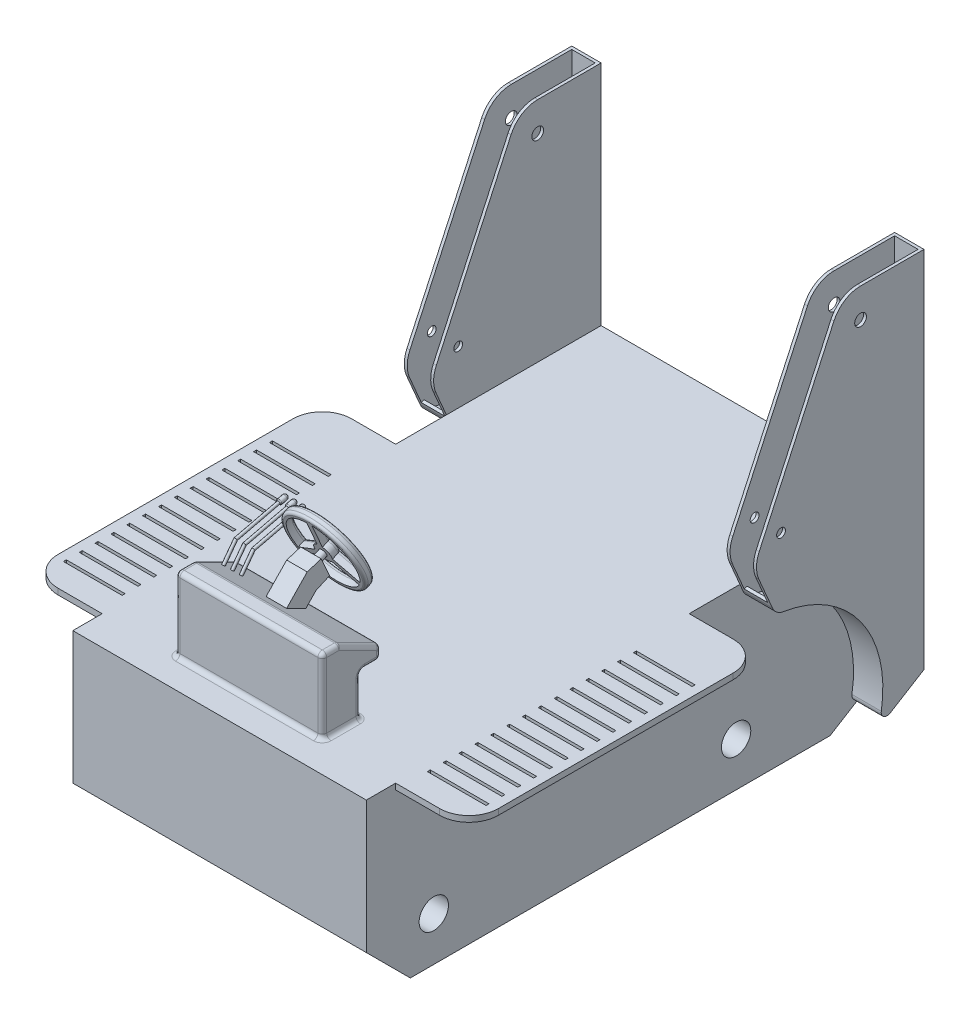
SolidWorks part; units mm, degrees
ref_plane "Front Plane" through (0, 0, 0) normal (0, 0, 1) x (1, 0, 0)
ref_plane "Top Plane" through (0, 0, 0) normal (0, 1, 0) x (1, 0, 0)
ref_plane "Right Plane" through (0, 0, 0) normal (1, 0, 0) x (0, 0, -1)
sketch "Sketch2" plane through (0, 0, 0) normal (1, 0, 0) x (0, 0, -1)
  line L0 (-865, 600) -> (935, 600)
  line L1 (935, 600) -> (935, 135)
  line L2 (935, 135) -> (715, 0)
  line L3 (715, 0) -> (-715, 0)
  line L4 (-715, 0) -> (-865, 150)
  line L5 (-865, 150) -> (-865, 600)
  circle A0 centre (-635, 150) radius 50
  circle A1 centre (395, 150) radius 50
  dimension "D8" = 100
  dimension "D1" = 1800
  dimension "D2" = 600
  dimension "D3" = 150
  dimension "D4" = 150
  dimension "D5" = 220
  dimension "D6" = 135
  dimension "D7" = 1030
  dimension "D9" = 150
  dimension "D10" = 540
extrude "Boss-Extrude1" add sketch "Sketch2" along normal mid plane 1000
sketch "Sketch3" plane through (500, 0, 0) normal (1, 0, 0) x (0, 0, -1)
  line L0 (935, 135) -> (935, 1375)
  line L1 (935, 1375) -> (719.0464, 1375)
  line L2 (628.213, 1316.8244) -> (373.5875, 763.8338)
  line L3 (372.5065, 682.6174) -> (418.6781, 574.8835)
  line L4 (935, 135) -> (819.8142, 64.3178)
  line L5 (715, 0) -> (935, 135) construction
  arc A0 (819.8142, 64.3178) -> (789.6227, 84.6326) centre (809.3539, 81.3643) cw
  arc A1 (789.6227, 84.6326) -> (456.8981, 545.1818) centre (395, 150) ccw
  circle A2 centre (395, 150) radius 50 construction
  arc A3 (719.0464, 1375) -> (628.213, 1316.8244) centre (719.0464, 1275) ccw
  arc A4 (373.5875, 763.8338) -> (372.5065, 682.6174) centre (464.421, 722.0093) ccw
  arc A5 (418.6781, 574.8835) -> (456.8981, 545.1818) centre (464.6354, 594.5795) ccw
  point P16 (655, 1375)
  point P19 (355, 723.4658)
  point P22 (430, 548.4658)
  dimension "D5" = 400
  dimension "D6" = 20
  dimension "D8" = 100
  dimension "D9" = 100
  dimension "D10" = 50
  dimension "D1" = 1240
  dimension "D2" = 280
  dimension "D3" = 175
  dimension "D4" = 75
  dimension "D7" = 35
extrude "Boss-Extrude2" add sketch "Sketch3" along normal blind 10 separate body
sketch "Sketch5" plane through (510, 0, 0) normal (1, 0, 0) x (0, 0, -1)
  line L0 (935, 135) -> (935, 1375) construction
  line L1 (935, 600) -> (-865, 600) construction
  line L2 (935, 135) -> (935, 1375)
  line L3 (819.8142, 64.3178) -> (935, 135) construction
  line L4 (819.8142, 64.3178) -> (935, 135)
  line L5 (418.6781, 574.8835) -> (412.6282, 589)
  line L6 (372.5065, 682.6174) -> (418.6781, 574.8835) construction
  line L7 (427.8696, 578.8227) -> (421.8197, 592.9392)
  line L8 (814.584, 72.841) -> (925, 140.5963)
  line L9 (925, 140.5963) -> (925, 1375)
  line L10 (418.6781, 574.8835) -> (411.5081, 591.6137) construction
  line L11 (427.8696, 578.8227) -> (420.6995, 595.5529) construction
  line L12 (412.6282, 589) -> (421.8197, 592.9392)
  line L13 (925, 1375) -> (935, 1375)
  arc A1 (789.6227, 84.6326) -> (819.8142, 64.3178) centre (809.3539, 81.3643) ccw construction
  arc A2 (789.6227, 84.6326) -> (819.8142, 64.3178) centre (809.3539, 81.3643) ccw
  arc A3 (789.6227, 84.6326) -> (456.8981, 545.1818) centre (395, 150) ccw construction
  arc A4 (789.6227, 84.6326) -> (456.8981, 545.1818) centre (395, 150) ccw
  arc A5 (418.6781, 574.8835) -> (456.8981, 545.1818) centre (464.6354, 594.5795) ccw construction
  arc A6 (418.6781, 574.8835) -> (456.8981, 545.1818) centre (464.6354, 594.5795) ccw
  arc A7 (427.8696, 578.8227) -> (458.4456, 555.0613) centre (464.6354, 594.5795) ccw
  arc A8 (799.4883, 82.9984) -> (458.4456, 555.0613) centre (395, 150) ccw
  arc A9 (799.4883, 82.9984) -> (814.584, 72.841) centre (809.3539, 81.3643) ccw
  dimension "D2" = 11
  dimension "D1" = 10
extrude "Boss-Extrude3" add sketch "Sketch5" along normal blind 80
extrude "Boss-Extrude4" add sketch "Sketch3<2>" along normal blind 10 from offset 90
sketch "Sketch3<2>" plane through (500, 0, 0) normal (1, 0, 0) x (0, 0, -1) same geometry as "Sketch3"
mirror "Mirror7" about plane through (0, 0, 0) normal (1, 0, 0) of bodies 104
sketch "Sketch6" plane through (600, 0, 0) normal (1, 0, 0) x (0, 0, -1)
  line L0 (628.213, 1316.8244) -> (373.5875, 763.8338) construction
  circle A0 centre (719.0464, 1275) radius 20
  circle A1 centre (448.0114, 782.0093) radius 15
  arc A2 (373.5875, 763.8338) -> (372.5065, 682.6174) centre (464.421, 722.0093) ccw construction
  dimension "D1" = 30
  dimension "D3" = 60
  dimension "D4" = 40
  dimension "D2" = 60
extrude "Cut-Extrude1" cut sketch "Sketch6" against normal through all
sketch "Sketch7" plane through (0, 600, 0) normal (0, 1, 0) x (1, 0, 0)
  line L0 (0, 0) -> (0, -865) construction
  line L1 (500, -865) -> (-500, -865) construction
  line L2 (500, 935) -> (500, -865) construction
  line L3 (500, 235) -> (650, 235)
  line L4 (500, 235) -> (500, -765)
  line L5 (500, -765) -> (650, -765)
  line L6 (750, 135) -> (750, -665)
  line L7 (-750, 135) -> (-750, -665)
  line L8 (-500, -765) -> (-650, -765)
  line L9 (-500, 235) -> (-500, -765)
  line L10 (-500, 235) -> (-650, 235)
  arc A0 (650, -765) -> (750, -665) centre (650, -665) ccw
  arc A1 (650, 235) -> (750, 135) centre (650, 135) cw
  arc A2 (-650, 235) -> (-750, 135) centre (-650, 135) ccw
  arc A3 (-650, -765) -> (-750, -665) centre (-650, -665) cw
  point P13 (750, -765)
  point P16 (750, 235)
  point P25 (-750, 235)
  point P26 (-750, -765)
  dimension "D4" = 100
  dimension "D1" = 250
  dimension "D2" = 100
  dimension "D3" = 1000
extrude "Boss-Extrude6" add sketch "Sketch7" against normal blind 20
sketch "Sketch8" plane through (0, 600, 0) normal (0, 1, 0) x (1, 0, 0)
  line L0 (750, -665) -> (750, 135) construction
  line L1 (520, 35) -> (720, 35)
  line L2 (520, 35) -> (520, 25)
  line L3 (520, 25) -> (720, 25)
  line L4 (720, 35) -> (720, 25)
  line L5 (650, 235) -> (500, 235) construction
  line L6 (0, 0) -> (0, -250.1496) construction
  line L7 (-720, 35) -> (-720, 25)
  line L8 (-520, 25) -> (-720, 25)
  line L9 (-520, 35) -> (-520, 25)
  line L10 (-520, 35) -> (-720, 35)
  dimension "D1" = 200
  dimension "D2" = 30
  dimension "D3" = 10
  dimension "D4" = 200
extrude "Cut-Extrude2" cut sketch "Sketch8" against normal through all
pattern_linear "LPattern1" count 14 spacing 54 along (0, 0, 1) of "Cut-Extrude2"
sketch "Sketch9" plane through (0, 600, 0) normal (0, 1, 0) x (1, 0, 0)
  line L0 (500, -865) -> (-500, -865) construction
  line L1 (-250, -565) -> (250, -565)
  line L2 (-250, -565) -> (-250, -765)
  line L3 (-250, -765) -> (250, -765)
  line L4 (250, -565) -> (250, -765)
  line L5 (0, -565) -> (0, -765) construction
  point P9 (0, -665)
  point P10 (0, -565)
  dimension "D1" = 500
  dimension "D2" = 200
  dimension "D3" = 100
extrude "Boss-Extrude7" add sketch "Sketch9" along normal blind 253
sketch "Sketch10" plane through (250, 0, 0) normal (1, 0, 0) x (0, 0, -1)
  line L0 (-705, 853) -> (-565, 853)
  line L1 (-765, 853) -> (-565, 853) construction
  line L2 (-565, 853) -> (-565, 783)
  line L3 (-565, 853) -> (-565, 600) construction
  line L4 (-565, 783) -> (-705, 853)
  line L5 (-565, 740) -> (-635, 740)
  line L6 (-635, 740) -> (-635, 600)
  line L7 (-765, 600) -> (-565, 600) construction
  line L8 (-635, 600) -> (-565, 600)
  line L9 (-565, 600) -> (-565, 740)
  dimension "D1" = 70
  dimension "D2" = 140
  dimension "D3" = 140
  dimension "D4" = 70
extrude "Cut-Extrude3" cut sketch "Sketch10" against normal through all
fillet "Fillet1" radius 15 21 edges at (0, 600, 635) (0, 740, 635) (0, 853, 705) (-250, 600, 700) (-250, 670, 635) (-250, 740, 600) (-250, 818, 635) (-250, 853, 735) (0, 740, 565) (0, 783, 565) (-250, 761.5, 565) (-250, 726.5, 765) (0, 853, 765) (0, 600, 765) (250, 740, 600) (250, 670, 635) (250, 600, 700) (250, 726.5, 765) (250, 853, 735) (250, 818, 635) (250, 761.5, 565)
ref_plane "Plane1" through (-220, 0, 0) normal (-1, 0, 0) x (0, 0, 1)
sketch "Sketch12" plane through (-220, 0, 0) normal (-1, 0, 0) x (0, 0, 1)
  line L0 (573.2918, 787.1459) -> (701.8328, 851.4164) construction
  line L1 (631.5477, 816.2738) -> (589.8462, 872.4965)
  line L2 (589.8462, 872.4965) -> (443.9511, 907.3477)
  dimension "D1" = 140
  dimension "D2" = 100
  dimension "D3" = 150
  dimension "D4" = 70
  dimension "D5" = 80
ref_plane "Plane2" through (-220, 907.3477, 443.9511) normal (0, 0.2323, -0.9726) x (-1, 0, 0)
sketch "Sketch13" plane through (-220, 907.3477, 443.9511) normal (0, 0.2323, -0.9726) x (-1, 0, 0)
  circle A0 centre (0, 0) radius 5
  dimension "D1" = 10
sweep "Sweep1" add profiles "Sketch13" path "Sketch12"
sketch "Sketch14" plane through (-220, 907.3477, 443.9511) normal (0, 0.2323, -0.9726) x (-1, 0, 0)
  circle A0 centre (0, 0) radius 8.5
  dimension "D1" = 17
extrude "Boss-Extrude8" add sketch "Sketch14" along normal blind 30
fillet "Fillet2" radius 8.5 1 edges at (-220, 922.5853, 416.7469)
fillet "Fillet3" radius 3.5 1 edges at (-220, 915.6151, 445.926)
pattern_linear "LPattern2" count 3 spacing 30 along (1, 0, 0) of bodies 115
sketch "Sketch16" plane through (0, 0, 0) normal (1, 0, 0) x (0, 0, -1)
  line L0 (-671.4223, 836.2111) -> (-601.352, 908.9514)
  line L1 (-701.8328, 851.4164) -> (-573.2918, 787.1459) construction
  line L2 (-601.352, 908.9514) -> (-553.5549, 923.6293)
  line L3 (-553.5549, 923.6293) -> (-525.3675, 859.5553)
  line L4 (-525.3675, 859.5553) -> (-571.1346, 839.4215)
  line L5 (-571.1346, 839.4215) -> (-605.8229, 803.4115)
  line L6 (-605.8229, 803.4115) -> (-671.4223, 836.2111)
  line L7 (-708.541, 838) -> (-701.8328, 851.4164) construction
  dimension "D1" = 101
  dimension "D2" = 151
  dimension "D3" = 50
  dimension "D4" = 70
  dimension "D5" = 34
  dimension "D6" = 70
extrude "Boss-Extrude9" add sketch "Sketch16" along normal mid plane 70
sketch "Sketch17" plane through (0, -54.2681, 123.3593) normal (0, 0.4027, -0.9153) x (-1, 0, 0)
  line L0 (-35, 1068.3406) -> (35, 1068.3406) construction
  line L1 (35, 998.3406) -> (35, 1068.3406) construction
  circle A0 centre (0, 1033.3406) radius 12.5
  dimension "D1" = 25
  dimension "D2" = 35
  dimension "D3" = 35
extrude "Boss-Extrude10" add sketch "Sketch17" along normal blind 30
sketch "Sketch18" plane through (0, -42.1878, 95.899) normal (0, 0.4027, -0.9153) x (-1, 0, 0)
  line L2 (-9, 1149.9939) -> (-9, 1061.9587)
  line L3 (9, 1149.9939) -> (9, 1061.9587)
  line L4 (105.5247, 982.8081) -> (29.2841, 1026.8257)
  line L5 (96.5247, 967.2197) -> (20.2841, 1011.2372)
  line L6 (-96.5247, 967.2197) -> (-20.2841, 1011.2372)
  line L7 (-105.5247, 982.8081) -> (-29.2841, 1026.8257)
  circle A0 centre (0, 1033.3406) radius 135
  arc A1 (-9, 1149.9939) -> (-105.5247, 982.8081) centre (0, 1033.3406) ccw
  arc A2 (29.2841, 1026.8257) -> (9, 1061.9587) centre (0, 1033.3406) ccw
  arc A4 (-96.5247, 967.2197) -> (96.5247, 967.2197) centre (0, 1033.3406) ccw
  arc A5 (105.5247, 982.8081) -> (9, 1149.9939) centre (0, 1033.3406) ccw
  arc A6 (-9, 1061.9587) -> (-29.2841, 1026.8257) centre (0, 1033.3406) ccw
  arc A7 (-20.2841, 1011.2372) -> (20.2841, 1011.2372) centre (0, 1033.3406) ccw
  circle A8 centre (0, 1033.3406) radius 12.5 construction
  point P24 (0, 1033.3406)
  dimension "D1" = 18
  dimension "D2" = 270
  dimension "D3" = 60
  dimension "D4" = 18
  dimension "D5" = 3
extrude "Boss-Extrude11" add sketch "Sketch18" along normal blind 30
fillet "Fillet4" radius 9 13 edges at (25.9808, 929.483, 490.5808) (9, 982.2395, 513.7894) (101.325, 969.3004, 508.0972) (67.4044, 889.644, 473.0549) (-101.325, 969.3004, 508.0972) (-9, 982.2395, 513.7894) (-25.9808, 929.483, 490.5808) (-67.4044, 889.644, 473.0549) (0, 808.6578, 437.4275) (-58.4044, 875.3752, 466.7778) (0, 888.2926, 472.4604) (58.4044, 875.3752, 466.7778) (0, 1039.3241, 538.902)
fillet "Fillet5" radius 9 1 edges at (0, 1027.2438, 566.3623)
